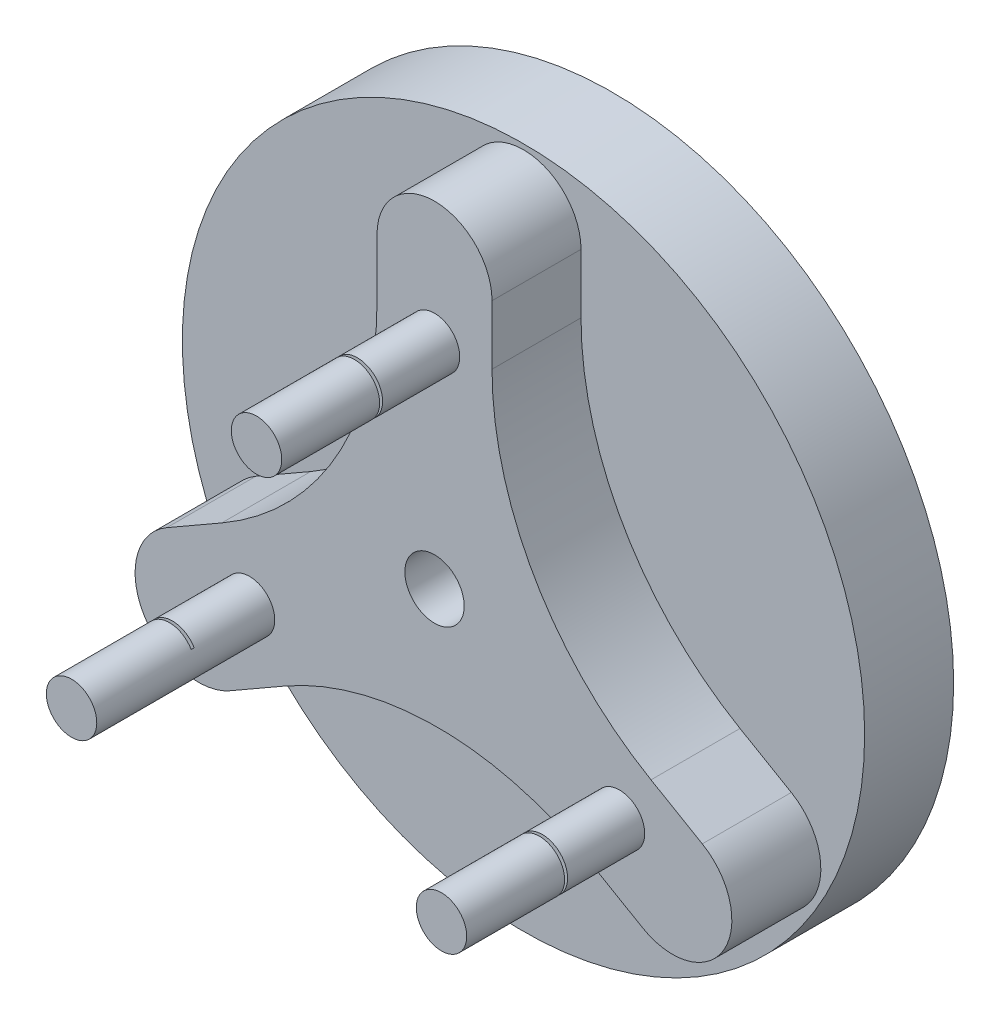
SolidWorks part; units mm, degrees
note: '?' marks a value the reader was unsure of.
ref_plane "Plan de face" through (0, 0, 0) normal (0, 0, 1) x (1, 0, 0)
ref_plane "Plan de dessus" through (0, 0, 0) normal (0, 1, 0) x (1, 0, 0)
ref_plane "Plan de droite" through (0, 0, 0) normal (1, 0, 0) x (0, 0, -1)
sketch "Esquisse1" plane through (0, 0, 0) normal (0, 0, 1) x (1, 0, 0)
  line L0 (0, 130) -> (0, 113.224) construction
  line L1 (-90.226, -27.2083) -> (-71.7242, -16.5838)
  line L2 (0, 130) -> (0, 0) construction
  line L3 (-72.3884, 113.224) -> (67.6116, 113.224) construction
  line L4 (-112.612, -64.6658) -> (0, 0) construction
  line L5 (-68.9772, -64.2119) -> (-50.4754, -53.5875)
  line L6 (-56.2374, -129.242) -> (-139.9696, 16.573) construction
  line L7 (24.3109, 113.224) -> (19.3835, 93.8405) construction
  line L8 (100.0395, -52.289) -> (87.5124, -73.8698) construction
  line L9 (-24.3109, 113.224) -> (-19.3835, 93.8405) construction
  line L10 (19.3835, 93.8405) -> (-19.3835, 93.8405) construction
  line L11 (-108.7279, -37.8327) -> (-71.7242, -16.5838) construction
  line L12 (90.2728, -29.2757) -> (100.0395, -52.289) construction
  line L13 (70.1918, -63.8698) -> (87.5124, -73.8698) construction
  line L14 (-87.4791, -74.8363) -> (-50.4754, -53.5875) construction
  line L17 (0, 0) -> (112.4309, -65.2632) construction
  line L20 (90.2728, -29.2757) -> (72.9757, -19.2352)
  line L23 (70.1918, -63.8698) -> (52.8948, -53.8293)
  line L25 (-19.3835, 93.8405) -> (-19.3835, 73.8405)
  line L27 (19.3835, 93.8405) -> (19.3835, 73.8405)
  arc A16 (-19.3835, 93.8405) -> (19.3835, 93.8405) centre (0, 93.8405) cw
  arc A18 (90.2728, -29.2757) -> (70.1918, -63.8698) centre (80.2323, -46.5727) cw
  arc A27 (-19.3835, 73.8405) -> (-71.7242, -16.5838) centre (-123.6422, 73.8285) cw
  arc A28 (19.3835, 73.8405) -> (72.9757, -19.2352) centre (127.0037, 73.8405) ccw
  arc A30 (-90.226, -27.2083) -> (-68.9772, -64.2119) centre (-79.6016, -45.7101) ccw
  circle A32 centre (0, 0) radius 10
  arc A33 (-50.4754, -53.5875) -> (52.8948, -53.8293) centre (1.0003, -143.2296) cw
  circle A44 centre (0, 0) radius 115
  point P17 (97.5294, -56.6132)
  point P66 (-98.1035, -56.3345)
  dimension "D2" = 230
  dimension "D4" = 120
  dimension "D6" = 20
  dimension "D7" = 20
  dimension "D10" = 20
  dimension "D11" = 25
  dimension "D12" = 20
extrude "Boss.-Extru.1" add sketch "Esquisse1" along normal blind 30
ref_plane "Plan1" through (0, 0, 0) normal (0, 0, -1) x (-1, 0, 0)
sketch "Esquisse4" plane through (0, 0, 0) normal (0, 0, 1) x (1, 0, 0)
  line L0 (0, 130) -> (0, 113.224) construction
  line L1 (-90.226, -27.2083) -> (-71.7242, -16.5838)
  line L2 (0, 130) -> (0, 0) construction
  line L3 (-72.3884, 113.224) -> (67.6116, 113.224) construction
  line L4 (-112.612, -64.6658) -> (0, 0) construction
  line L5 (-68.9772, -64.2119) -> (-50.4754, -53.5875)
  line L6 (-56.2374, -129.242) -> (-139.9696, 16.573) construction
  line L7 (24.3109, 113.224) -> (19.3835, 93.8405) construction
  line L8 (100.0395, -52.289) -> (87.5124, -73.8698) construction
  line L9 (-24.3109, 113.224) -> (-19.3835, 93.8405) construction
  line L10 (19.3835, 93.8405) -> (-19.3835, 93.8405) construction
  line L11 (-108.7279, -37.8327) -> (-71.7242, -16.5838) construction
  line L12 (90.2728, -29.2757) -> (100.0395, -52.289) construction
  line L13 (70.1918, -63.8698) -> (87.5124, -73.8698) construction
  line L14 (-87.4791, -74.8363) -> (-50.4754, -53.5875) construction
  line L17 (0, 0) -> (112.4309, -65.2632) construction
  line L20 (90.2728, -29.2757) -> (72.9757, -19.2352)
  line L23 (70.1918, -63.8698) -> (52.8948, -53.8293)
  line L25 (-19.3835, 93.8405) -> (-19.3835, 73.8405)
  line L27 (19.3835, 93.8405) -> (19.3835, 73.8405)
  arc A16 (-19.3835, 93.8405) -> (19.3835, 93.8405) centre (0, 93.8405) cw
  arc A18 (90.2728, -29.2757) -> (70.1918, -63.8698) centre (80.2323, -46.5727) cw
  arc A27 (-19.3835, 73.8405) -> (-71.7242, -16.5838) centre (-123.6422, 73.8285) cw
  arc A28 (19.3835, 73.8405) -> (72.9757, -19.2352) centre (127.0037, 73.8405) ccw
  arc A30 (-90.226, -27.2083) -> (-68.9772, -64.2119) centre (-79.6016, -45.7101) ccw
  circle A32 centre (0, 0) radius 10
  arc A33 (-50.4754, -53.5875) -> (52.8948, -53.8293) centre (1.0003, -143.2296) cw
  circle A44 centre (0, 0) radius 115
extrude "Boss.-Extru.3" add sketch "Esquisse4" along normal blind 60
ref_plane "Plan2" through (0, 0, 60) normal (0, 0, 1) x (1, 0, 0)
sketch "Esquisse7" plane through (0, 0, 60) normal (0, 0, 1) x (1, 0, 0)
  line L0 (0, 0) -> (0, 146.7652) construction
  line L1 (0, 0) -> (-184.2878, -106.3986) construction
  line L2 (0, 0) -> (132.8812, -76.719) construction
  circle A0 centre (0, 72) radius 8.5
  dimension "D3" = 17
  dimension "D4" = 72
  dimension "D1" = 120
  dimension "D2" = 120
extrude "Boss.-Extru.4" add sketch "Esquisse7" along normal blind 60
ref_axis "Axe1" through (0, 0, 30) along (0, 0, -1)?
pattern_circular "Répétition circulaire1" count 3 every 120 about axis through (0, 0, 0) along (0, 0, 1) of "Boss.-Extru.4"
sketch "Esquisse8" plane through (0, 0, 120) normal (0, 0, 1) x (1, 0, 0)
  line L0 (0, 0) -> (0, 139.6896) construction
  line L1 (0, 0) -> (-98.1035, -56.3345) construction
  circle A0 centre (0, 72) radius 7
  circle A1 centre (0, 72) radius 8.5
  circle A2 centre (-62.4379, -35.854) radius 8.5
  circle A3 centre (-62.4379, -35.854) radius 7
  circle A4 centre (62.3538, -36) radius 8.5
  circle A5 centre (62.3538, -36) radius 7
  arc A11 (-90.226, -27.2083) -> (-68.9772, -64.2119) centre (-79.6016, -45.7101) ccw construction
  point P2 (0, 0)
  dimension "D1" = 72
  dimension "D2" = 72
  dimension "D3" = 14
extrude "Enlèv. mat.-Extru.1" cut sketch "Esquisse8" against normal blind 1 from offset 33 offset against normal yes
sketch "Esquisse10" plane through (0, 0, 0) normal (0, 0, -1) x (-1, 0, 0)
  circle A0 centre (0, 0) radius 105
  dimension "D1" = 210
extrude "Enlèv. mat.-Extru.2" cut sketch "Esquisse10" against normal blind 20 from offset 5 offset against normal yes
scale "Echelle1" scale about centroid uniform scaling yes scale factor 0.25
